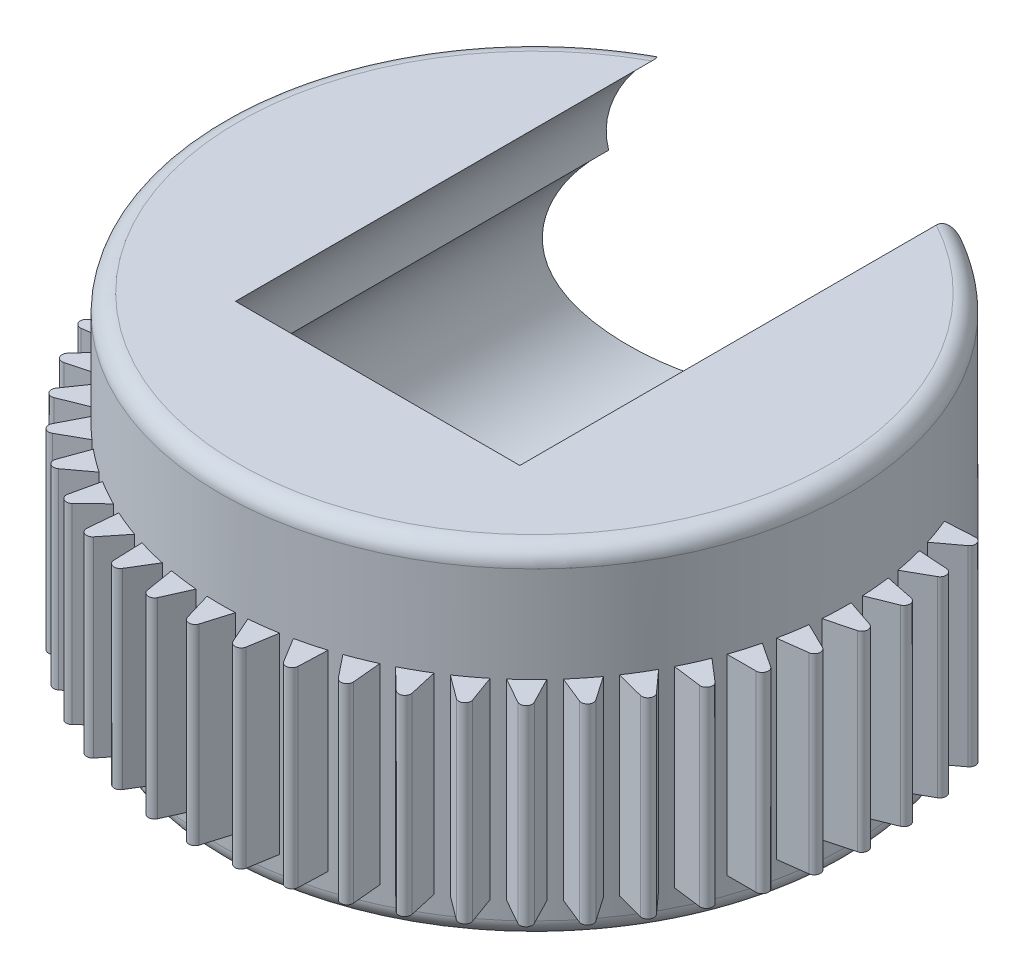
SolidWorks part; units mm, degrees
ref_plane "Спереди" through (0, 0, 0) normal (0, 0, 1) x (1, 0, 0)
ref_plane "Сверху" through (0, 0, 0) normal (0, 1, 0) x (1, 0, 0)
ref_plane "Справа" through (0, 0, 0) normal (1, 0, 0) x (0, 0, -1)
sketch "Эскиз1" plane through (0, 0, 0) normal (0, 1, 0) x (1, 0, 0)
  circle A0 centre (0, 0) radius 18
  dimension "D1" = 36
extrude "Бобышка-Вытянуть1" add sketch "Эскиз1" along normal blind 19.5
sketch "Эскиз2" plane through (0, 19.5, 0) normal (0, 1, 0) x (1, 0, 0)
  circle A0 centre (0, 0) radius 4.5
  dimension "D1" = 9
extrude "Вырез-Вытянуть1" cut sketch "Эскиз2" against normal through all
sketch "Эскиз3" plane through (0, 0, 0) normal (0, 0, 1) x (1, 0, 0)
  line L0 (-6.5, 9.5) -> (6.5, 9.5) construction
  line L2 (-6.5, 3.5) -> (6.5, 3.5)
  line L3 (-5, 15) -> (5, 15) construction
  line L4 (-5, 20.5) -> (5, 20.5)
  arc A0 (-10.4165, 14.0454) -> (-6.5, 3.5) centre (-6.5, 9.5) ccw
  arc A1 (6.5, 3.5) -> (10.4165, 14.0454) centre (6.5, 9.5) ccw
  arc A2 (-5, 20.5) -> (-10.4165, 14.0454) centre (-5, 15) ccw
  arc A3 (10.4165, 14.0454) -> (5, 20.5) centre (5, 15) ccw
  point P2 (0, 9.5)
  point P9 (0, 15)
  dimension "D1" = 13
  dimension "D2" = 3.5
  dimension "D4" = 15
  dimension "D5" = 10
extrude "Вырез-Вытянуть2" cut sketch "Эскиз3" against normal through all and the other way blind 9
ref_plane "Плоскость1" through (0, 2, 0) normal (0, -1, 0) x (-1, 0, 0)
sketch "Эскиз4" plane through (0, 2, 0) normal (0, -1, 0) x (-1, 0, 0)
  line L3 (0.9, -17.7) -> (0.3352, -19.5825)
  line L4 (-0.3352, -19.5825) -> (-0.9, -17.7)
  line L5 (-0.9, -17.7) -> (0.9, -17.7)
  arc A0 (0.3352, -19.5825) -> (-0.3352, -19.5825) centre (0, -19.482) cw
  point P3 (0, -20.7)
  dimension "D1" = 0.35
  dimension "D4" = 17.7
  dimension "D5" = 1.8
  dimension "D6" = 3
extrude "Бобышка-Вытянуть2" add sketch "Эскиз4" against normal blind 11
ref_axis "Ось1" through (0, 19.5, 0) along (0, -1, 0)
pattern_circular "Круговой массив1" count 16 over 110 about axis through (0, 19.5, 0) along (0, -1, 0) of "Бобышка-Вытянуть2"
pattern_circular "Круговой массив2" count 16 over 110 about axis through (0, 19.5, 0) along (0, -1, 0) of "Бобышка-Вытянуть2" reverse direction yes
fillet "Скругление1" radius 1 1 edges at (0, 0, 18)
fillet "Скругление2" radius 1 1 edges at (0, 19.5, 18)
sketch "Эскиз5" plane through (0, 0, 0) normal (0, -1, 0) x (1, 0, 0)
  line L3 (-6.4071, 0) -> (8.4992, 0) construction
  line L4 (0.75, 13.357) -> (-0.75, 13.357)
  line L5 (0, 15.357) -> (0.75, 13.357)
  line L6 (-0.75, 13.357) -> (0, 15.357)
extrude "Бобышка-Вытянуть3" add sketch "Эскиз5" along normal blind 0.3
chamfer "Фаска1" distance 2.5 angle 45 1 edges at (0, 0, 4.5)
